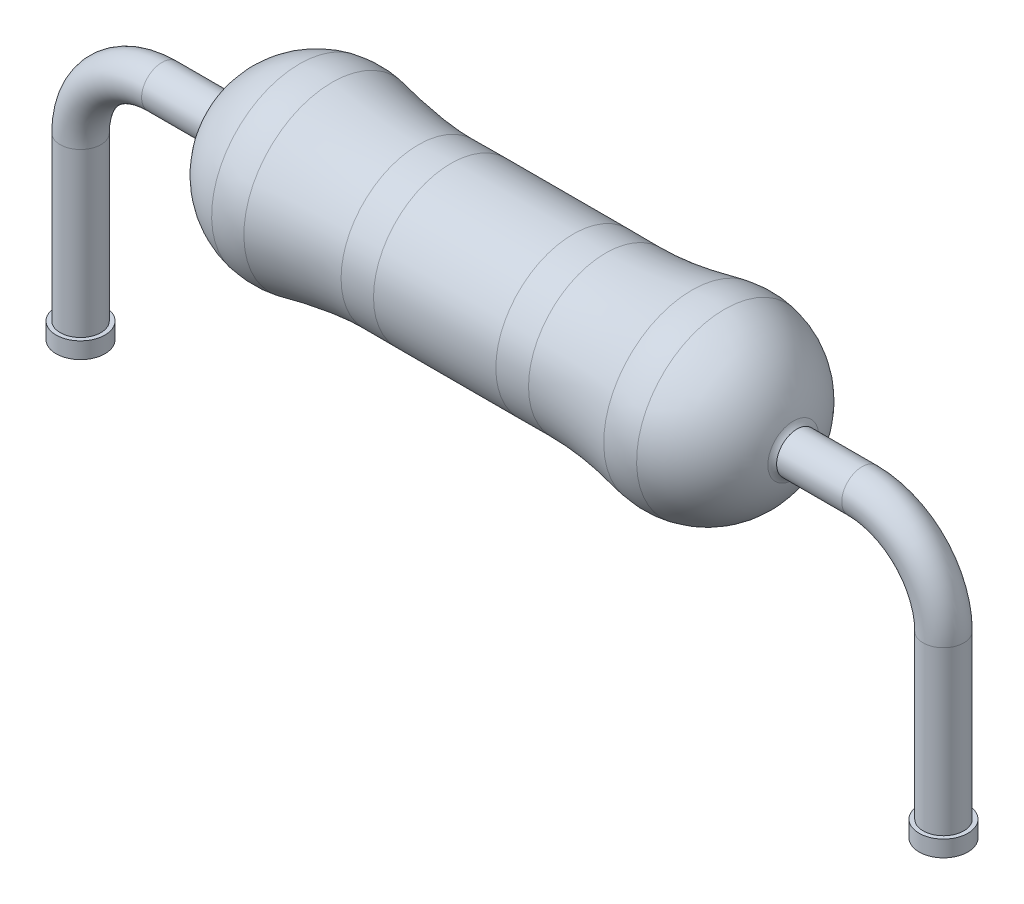
SolidWorks part; units mm, degrees
ref_plane "Front Plane" through (0, 0, 0) normal (0, 0, 1) x (1, 0, 0)
ref_plane "Top Plane" through (0, 0, 0) normal (0, 1, 0) x (1, 0, 0)
ref_plane "Right Plane" through (0, 0, 0) normal (1, 0, 0) x (0, 0, -1)
sketch "Sketch1" plane through (0, 0, 0) normal (0, 0, 1) x (1, 0, 0)
  line L0 (-3.5, 0) -> (3.5, 0) construction
  line L1 (3.5, 0) -> (3.5, 0.25)
  line L2 (0, 2.5431) -> (0, -1.0375) construction
  line L3 (0, 0.95) -> (3.7461, 0.95) construction
  line L4 (-0.7513, 0.95) -> (0.7513, 0.95)
  line L5 (-3.5, 0) -> (-3.5, 0.25)
  line L6 (-3.5, 0) -> (3.5, 0)
  line L7 (-6.2237, 0) -> (7.993, 0) construction
  arc A0 (-3.4548, 0.3122) -> (-2.2101, 1.0835) centre (-2.4, 0) cw
  arc A1 (3.4548, 0.3122) -> (2.2101, 1.0835) centre (2.4, 0) ccw
  spline S0 degree 2 poles (3.5, 0.25) (3.4713, 0.2767) (3.4548, 0.3122) knots 0 0 0 1 1 1
  spline S1 degree 3 poles (0.7513, 0.95) (0.9227, 0.9541) (1.4135, 0.928) (1.8981, 1.0175) (2.2101, 1.0835) knots 0 0 0 0 0.350784 1 1 1 1
  spline S2 degree 2 poles (-3.5, 0.25) (-3.4713, 0.2767) (-3.4548, 0.3122) knots 0 0 0 1 1 1
  spline S3 degree 3 poles (-0.7513, 0.95) (-0.9227, 0.9541) (-1.4135, 0.928) (-1.8981, 1.0175) (-2.2101, 1.0835) knots 0 0 0 0 0.350784 1 1 1 1
  dimension "D1" = 7
  dimension "D2" = 0.25
revolve "Revolve1" add sketch "Sketch1" angle 360 about L7
ref_plane "Plane1" through (0, 0, 2) normal (0, 0, 1) x (1, 0, 0)
sketch "Sketch2" plane through (0, 0, 2) normal (0, 0, 1) x (1, 0, 0)
  line L0 (0, 2.8244) -> (0, -3.3302) construction
  line L1 (-0.7513, 0.95) -> (-0.7513, -0.95) construction
  line L2 (-2.2101, 1.0835) -> (-2.2101, -1.0835) construction
  line L3 (0.7513, 0.95) -> (0.7513, -0.95) construction
  line L4 (2.2101, 1.0835) -> (2.2101, -1.0835) construction
  line L6 (2.2101, 2.9716) -> (2.6101, 2.9716)
  line L7 (2.2101, 2.9716) -> (2.2101, -2.4475)
  line L8 (2.2101, -2.4475) -> (2.6101, -2.4475)
  line L9 (2.6101, 2.9716) -> (2.6101, -2.4475)
  line L10 (0.7513, 2.9682) -> (1.1513, 2.9682)
  line L11 (0.7513, 2.9682) -> (0.7513, -2.4475)
  line L12 (0.7513, -2.4475) -> (1.1513, -2.4475)
  line L13 (1.1513, 2.9682) -> (1.1513, -2.4475)
  line L14 (-1.1513, 3.0104) -> (-0.7513, 3.0104)
  line L15 (-1.1513, 3.0104) -> (-1.1513, -2.5021)
  line L16 (-1.1513, -2.5021) -> (-0.7513, -2.5021)
  line L17 (-0.7513, 3.0104) -> (-0.7513, -2.5021)
  line L18 (-2.6101, 2.9976) -> (-2.2101, 2.9976)
  line L19 (-2.6101, 2.9976) -> (-2.6101, -2.5148)
  line L20 (-2.6101, -2.5148) -> (-2.2101, -2.5148)
  line L21 (-2.2101, 2.9976) -> (-2.2101, -2.5148)
  dimension "D1" = 0
  dimension "D2" = 0
  dimension "D3" = 0.4
  dimension "D4" = 0.4
  dimension "D5" = 0
  dimension "D6" = 0.4
  dimension "D7" = 0.4
  dimension "D8" = 0
split line "Split Line1"
sketch "Sketch3" plane through (-3.5, 0, 0) normal (-1, 0, 0) x (0, 0, 1)
  circle A0 centre (0, 0) radius 0.25
sketch "Sketch5" plane through (0, 0, 0) normal (0, 0, 1) x (1, 0, 0)
  line L0 (-3.5, 0) -> (-4.3, 0)
  line L1 (-5.3, -1) -> (-5.3, -3)
  arc A0 (-4.3, 0) -> (-5.3, -1) centre (-4.3, -1) ccw
  point P7 (-5.3, 0)
  dimension "D3" = 1
  dimension "D1" = 2
sweep "Sweep1" add profiles "Sketch3" path "Sketch5"
sketch "Sketch14" plane through (3.5, 0, 0) normal (1, 0, 0) x (0, 0, -1)
  circle A0 centre (0, 0) radius 0.25
sketch "Sketch15" plane through (0, 0, 0) normal (0, 0, 1) x (1, 0, 0)
  line L0 (3.5, 0) -> (4.3, 0)
  line L1 (5.3, -1) -> (5.3, -3)
  arc A0 (4.3, 0) -> (5.3, -1) centre (4.3, -1) cw
  point P7 (5.3, 0)
  dimension "D3" = 1
  dimension "D1" = 1.8
  dimension "D2" = 2
sweep "Sweep2" add profiles "Sketch14" path "Sketch15"
sketch "Sketch16" plane through (0, -3, 0) normal (0, -1, 0) x (1, 0, 0)
  circle A0 centre (-5.3, 0) radius 0.3
  dimension "D1" = 0.6
extrude "Boss-Extrude1" add sketch "Sketch16" along normal blind 0.2 contours A0
sketch "Sketch17" plane through (0, -3, 0) normal (0, -1, 0) x (1, 0, 0)
  circle A0 centre (5.3, 0) radius 0.3
  dimension "D1" = 0.6
extrude "Boss-Extrude2" add sketch "Sketch17" along normal blind 0.2
